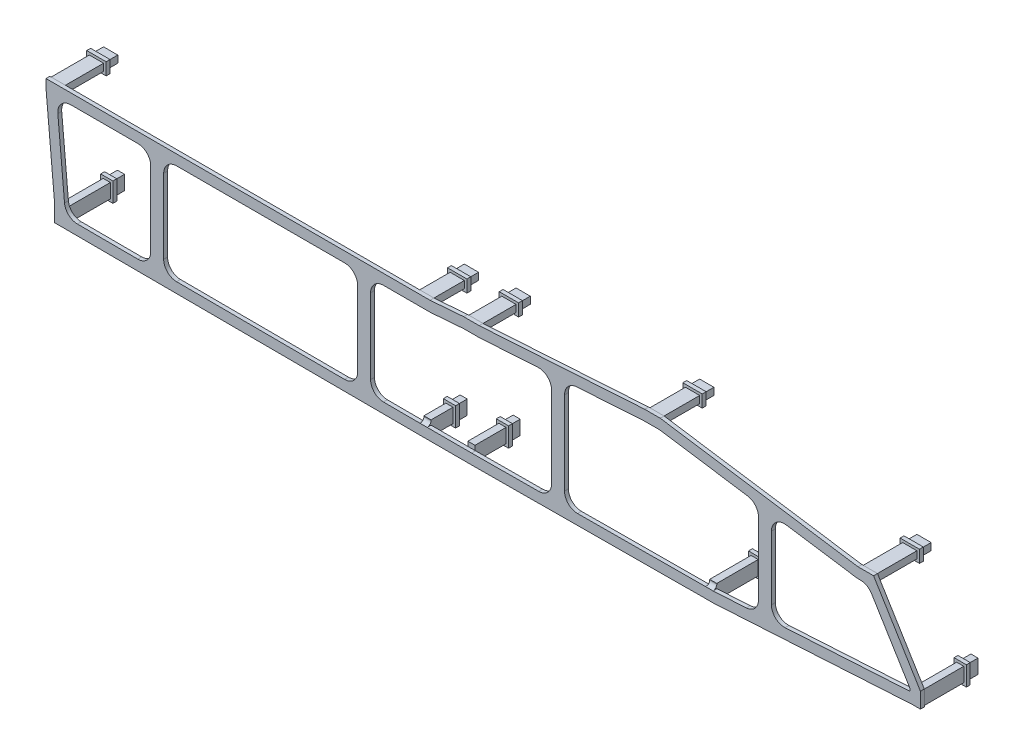
SolidWorks part; units mm, degrees
ref_plane "Front Plane" through (0, 0, 0) normal (0, 0, 1) x (1, 0, 0)
ref_plane "Top Plane" through (0, 0, 0) normal (0, 1, 0) x (1, 0, 0)
ref_plane "Right Plane" through (0, 0, 0) normal (1, 0, 0) x (0, 0, -1)
ref_plane "Plane11" through (0, 0, 7) normal (0, 0, 1) x (1, 0, 0)
ref_plane "Plane12" through (0, 0, 27) normal (0, 0, 1) x (1, 0, 0)
sketch "Sketch13" plane through (0, 0, 27) normal (0, 0, 1) x (1, 0, 0)
  line L0 (-277.75, -90) -> (-284.25, -90)
  line L1 (-284.25, -90) -> (-284.25, -78)
  line L2 (-284.25, -78) -> (-291, -3.25)
  line L3 (-291, -3.25) -> (-291, 3.25)
  line L4 (-291, 3.25) -> (-279, 3.25)
  line L5 (-279, 3.25) -> (-6, 3.25)
  line L6 (-6, 3.25) -> (6, 3.25)
  line L7 (6, 3.25) -> (32, 5.25)
  line L8 (32, 5.25) -> (44, 5.25)
  line L9 (44, 5.25) -> (172, 13.25)
  line L10 (172, 13.25) -> (184, 13.25)
  line L11 (184, 13.25) -> (337, -9.75)
  line L12 (337, -9.75) -> (349, -9.75)
  line L13 (349, -9.75) -> (385.25, -69)
  line L14 (385.25, -69) -> (385.25, -81)
  line L15 (385.25, -81) -> (378.75, -81)
  line L16 (378.75, -81) -> (225.25, -90)
  line L17 (225.25, -90) -> (218.75, -90)
  line L18 (218.75, -90) -> (38.25, -91)
  line L19 (38.25, -91) -> (31.75, -91)
  line L20 (31.75, -91) -> (4.25, -91)
  line L21 (4.25, -91) -> (-2.25, -91)
  line L22 (-2.25, -91) -> (-277.75, -90)
  line L23 (184, 13.25) -> (184, 6.75) construction
extrude "STUD LINK" add sketch "Sketch13" along normal blind 3
ref_plane "Plane1" through (0, 0, 0) normal (0, 0, 1) x (1, 0, 0)
ref_plane "Plane2" through (0, 0, -2) normal (0, 0, 1) x (1, 0, 0)
ref_plane "Plane3" through (0, 0, -4) normal (0, 0, 1) x (1, 0, 0)
ref_plane "Plane4" through (0, 0, 7) normal (0, 0, 1) x (1, 0, 0)
ref_plane "Plane5" through (0, 0, 0) normal (0, 0, 1) x (1, 0, 0)
ref_plane "Plane6" through (0, 0, -8) normal (0, 0, 1) x (1, 0, 0)
ref_plane "Plane7" through (0, 0, -7) normal (0, 0, 1) x (1, 0, 0)
ref_plane "Plane8" through (0, 0, -7) normal (0, 0, 1) x (1, 0, 0)
ref_plane "Plane9" through (0, 0, -6) normal (0, 0, 1) x (1, 0, 0)
ref_plane "Plane10" through (0, 0, -10) normal (0, 0, 1) x (1, 0, 0)
sketch "Sketch1" plane through (0, 0, 0) normal (0, 0, 1) x (1, 0, 0)
  line L8 (-5.5, 2.75) -> (-5.5, -2.75)
  line L9 (-5.5, -2.75) -> (5.5, -2.75)
  line L10 (5.5, -2.75) -> (5.5, 2.75)
  line L11 (5.5, 2.75) -> (-5.5, 2.75)
  line L12 (-5.5, 2.75) -> (-5.5, -2.75)
  line L13 (-5.5, -2.75) -> (5.5, -2.75)
  line L14 (5.5, -2.75) -> (5.5, 2.75)
  line L15 (5.5, 2.75) -> (-5.5, 2.75)
  dimension "D1" = 0.5
extrude "Boss-Extrude1" add sketch "Sketch1" against normal blind 8 and the other way up to next
sketch "Sketch2" plane through (0, 0, -2) normal (0, 0, 1) x (1, 0, 0)
  line L8 (43.5, 4.75) -> (32.5, 4.75)
  line L9 (43.5, -0.75) -> (43.5, 4.75)
  line L10 (32.5, -0.75) -> (43.5, -0.75)
  line L11 (32.5, 4.75) -> (32.5, -0.75)
  line L12 (43.5, 4.75) -> (32.5, 4.75)
  line L13 (43.5, -0.75) -> (43.5, 4.75)
  line L14 (32.5, -0.75) -> (43.5, -0.75)
  line L15 (32.5, 4.75) -> (32.5, -0.75)
  dimension "D1" = 0.5
extrude "Boss-Extrude2" add sketch "Sketch2" against normal blind 8 and the other way up to next separate body
sketch "Sketch3" plane through (0, 0, -4) normal (0, 0, 1) x (1, 0, 0)
  line L16 (183.5, 12.75) -> (172.5, 12.75)
  line L17 (183.5, 7.25) -> (183.5, 12.75)
  line L18 (172.5, 7.25) -> (183.5, 7.25)
  line L19 (172.5, 12.75) -> (172.5, 7.25)
  line L20 (183.5, 12.75) -> (172.5, 12.75)
  line L21 (183.5, 7.25) -> (183.5, 12.75)
  line L22 (172.5, 7.25) -> (183.5, 7.25)
  line L23 (172.5, 12.75) -> (172.5, 7.25)
  dimension "D1" = 0.5
extrude "Boss-Extrude3" add sketch "Sketch3" against normal blind 8 and the other way up to next separate body
sketch "Sketch4" plane through (0, 0, 7) normal (0, 0, 1) x (1, 0, 0)
  line L8 (3.75, -79.5) -> (-1.75, -79.5)
  line L9 (3.75, -90.5) -> (3.75, -79.5)
  line L10 (-1.75, -90.5) -> (3.75, -90.5)
  line L11 (-1.75, -79.5) -> (-1.75, -90.5)
  line L12 (3.75, -79.5) -> (-1.75, -79.5)
  line L13 (3.75, -90.5) -> (3.75, -79.5)
  line L14 (-1.75, -90.5) -> (3.75, -90.5)
  line L15 (-1.75, -79.5) -> (-1.75, -90.5)
  dimension "D1" = 0.5
extrude "Boss-Extrude4" add sketch "Sketch4" against normal blind 8 and the other way up to next separate body
sketch "Sketch5" plane through (0, 0, 0) normal (0, 0, 1) x (1, 0, 0)
  line L16 (32.25, -79.5) -> (32.25, -90.5)
  line L17 (37.75, -79.5) -> (32.25, -79.5)
  line L18 (37.75, -90.5) -> (37.75, -79.5)
  line L19 (32.25, -90.5) -> (37.75, -90.5)
  line L20 (32.25, -79.5) -> (32.25, -90.5)
  line L21 (37.75, -79.5) -> (32.25, -79.5)
  line L22 (37.75, -90.5) -> (37.75, -79.5)
  line L23 (32.25, -90.5) -> (37.75, -90.5)
  dimension "D1" = 0.5
extrude "Boss-Extrude5" add sketch "Sketch5" against normal blind 8 and the other way up to next separate body
sketch "Sketch6" plane through (0, 0, -8) normal (0, 0, 1) x (1, 0, 0)
  line L8 (224.75, -78.5) -> (219.25, -78.5)
  line L9 (219.25, -78.5) -> (219.25, -89.5)
  line L10 (219.25, -89.5) -> (224.75, -89.5)
  line L11 (224.75, -89.5) -> (224.75, -78.5)
  line L12 (224.75, -78.5) -> (219.25, -78.5)
  line L13 (219.25, -78.5) -> (219.25, -89.5)
  line L14 (219.25, -89.5) -> (224.75, -89.5)
  line L15 (224.75, -89.5) -> (224.75, -78.5)
  dimension "D1" = 0.5
extrude "Boss-Extrude6" add sketch "Sketch6" against normal blind 8 and the other way up to next separate body
sketch "Sketch7" plane through (0, 0, -7) normal (0, 0, 1) x (1, 0, 0)
  line L8 (348.5, -10.25) -> (337.5, -10.25)
  line L9 (348.5, -15.75) -> (348.5, -10.25)
  line L10 (337.5, -15.75) -> (348.5, -15.75)
  line L11 (337.5, -10.25) -> (337.5, -15.75)
  line L12 (348.5, -10.25) -> (337.5, -10.25)
  line L13 (348.5, -15.75) -> (348.5, -10.25)
  line L14 (337.5, -15.75) -> (348.5, -15.75)
  line L15 (337.5, -10.25) -> (337.5, -15.75)
  dimension "D1" = 0.5
extrude "Boss-Extrude7" add sketch "Sketch7" against normal blind 8 and the other way up to next separate body
sketch "Sketch8" plane through (0, 0, -7) normal (0, 0, 1) x (1, 0, 0)
  line L8 (384.75, -69.5) -> (379.25, -69.5)
  line L9 (384.75, -80.5) -> (384.75, -69.5)
  line L10 (379.25, -80.5) -> (384.75, -80.5)
  line L11 (379.25, -69.5) -> (379.25, -80.5)
  line L12 (384.75, -69.5) -> (379.25, -69.5)
  line L13 (384.75, -80.5) -> (384.75, -69.5)
  line L14 (379.25, -80.5) -> (384.75, -80.5)
  line L15 (379.25, -69.5) -> (379.25, -80.5)
  dimension "D1" = 0.5
extrude "Boss-Extrude8" add sketch "Sketch8" against normal blind 8 and the other way up to next separate body
sketch "Sketch9" plane through (0, 0, -6) normal (0, 0, 1) x (1, 0, 0)
  line L8 (-279.5, 2.75) -> (-290.5, 2.75)
  line L9 (-279.5, -2.75) -> (-279.5, 2.75)
  line L10 (-290.5, -2.75) -> (-279.5, -2.75)
  line L11 (-290.5, 2.75) -> (-290.5, -2.75)
  line L12 (-279.5, 2.75) -> (-290.5, 2.75)
  line L13 (-279.5, -2.75) -> (-279.5, 2.75)
  line L14 (-290.5, -2.75) -> (-279.5, -2.75)
  line L15 (-290.5, 2.75) -> (-290.5, -2.75)
  dimension "D1" = 0.5
extrude "Boss-Extrude9" add sketch "Sketch9" against normal blind 8 and the other way up to next separate body
sketch "Sketch10" plane through (0, 0, -10) normal (0, 0, 1) x (1, 0, 0)
  line L8 (-278.25, -78.5) -> (-283.75, -78.5)
  line L9 (-278.25, -89.5) -> (-278.25, -78.5)
  line L10 (-283.75, -89.5) -> (-278.25, -89.5)
  line L11 (-283.75, -78.5) -> (-283.75, -89.5)
  line L12 (-278.25, -78.5) -> (-283.75, -78.5)
  line L13 (-278.25, -89.5) -> (-278.25, -78.5)
  line L14 (-283.75, -89.5) -> (-278.25, -89.5)
  line L15 (-283.75, -78.5) -> (-283.75, -89.5)
  dimension "D1" = 0.5
extrude "Boss-Extrude10" add sketch "Sketch10" against normal blind 8 and the other way up to next (37 mm away) separate body
sketch "Sketch14" plane through (0, 0, 0) normal (0, 0, 1) x (1, 0, 0)
  line L8 (-7.5, -4.75) -> (7.5, -4.75)
  line L9 (7.5, -4.75) -> (7.5, 4.75)
  line L10 (7.5, 4.75) -> (-7.5, 4.75)
  line L11 (-7.5, 4.75) -> (-7.5, -4.75)
  line L12 (-7.5, -4.75) -> (7.5, -4.75)
  line L13 (7.5, -4.75) -> (7.5, 4.75)
  line L14 (7.5, 4.75) -> (-7.5, 4.75)
  line L15 (-7.5, 4.75) -> (-7.5, -4.75)
  dimension "D1" = 1.5
extrude "Boss-Extrude14" add sketch "Sketch14" along normal blind 3
sketch "Sketch15" plane through (0, 0, -2) normal (0, 0, 1) x (1, 0, 0)
  line L8 (45.5, 6.75) -> (30.5, 6.75)
  line L9 (30.5, 6.75) -> (30.5, -2.75)
  line L10 (30.5, -2.75) -> (45.5, -2.75)
  line L11 (45.5, -2.75) -> (45.5, 6.75)
  line L12 (45.5, 6.75) -> (30.5, 6.75)
  line L13 (30.5, 6.75) -> (30.5, -2.75)
  line L14 (30.5, -2.75) -> (45.5, -2.75)
  line L15 (45.5, -2.75) -> (45.5, 6.75)
  dimension "D1" = 1.5
extrude "Boss-Extrude15" add sketch "Sketch15" along normal blind 3
sketch "Sketch16" plane through (0, 0, -4) normal (0, 0, 1) x (1, 0, 0)
  line L16 (185.5, 14.75) -> (170.5, 14.75)
  line L17 (185.5, 5.25) -> (185.5, 14.75)
  line L18 (170.5, 5.25) -> (185.5, 5.25)
  line L19 (170.5, 14.75) -> (170.5, 5.25)
  line L20 (185.5, 14.75) -> (170.5, 14.75)
  line L21 (185.5, 5.25) -> (185.5, 14.75)
  line L22 (170.5, 5.25) -> (185.5, 5.25)
  line L23 (170.5, 14.75) -> (170.5, 5.25)
  dimension "D1" = 1.5
extrude "Boss-Extrude16" add sketch "Sketch16" along normal blind 3
sketch "Sketch17" plane through (0, 0, 7) normal (0, 0, 1) x (1, 0, 0)
  line L8 (5.75, -77.5) -> (-3.75, -77.5)
  line L9 (-3.75, -77.5) -> (-3.75, -92.5)
  line L10 (-3.75, -92.5) -> (5.75, -92.5)
  line L11 (5.75, -92.5) -> (5.75, -77.5)
  line L12 (5.75, -77.5) -> (-3.75, -77.5)
  line L13 (-3.75, -77.5) -> (-3.75, -92.5)
  line L14 (-3.75, -92.5) -> (5.75, -92.5)
  line L15 (5.75, -92.5) -> (5.75, -77.5)
  dimension "D1" = 1.5
extrude "Boss-Extrude17" add sketch "Sketch17" along normal blind 3
sketch "Sketch18" plane through (0, 0, 0) normal (0, 0, 1) x (1, 0, 0)
  line L8 (39.75, -77.5) -> (30.25, -77.5)
  line L9 (39.75, -92.5) -> (39.75, -77.5)
  line L10 (30.25, -92.5) -> (39.75, -92.5)
  line L11 (30.25, -77.5) -> (30.25, -92.5)
  line L16 (39.75, -77.5) -> (30.25, -77.5)
  line L17 (39.75, -92.5) -> (39.75, -77.5)
  line L18 (30.25, -92.5) -> (39.75, -92.5)
  line L19 (30.25, -77.5) -> (30.25, -92.5)
  dimension "D1" = 1.5
extrude "Boss-Extrude18" add sketch "Sketch18" along normal blind 3
sketch "Sketch19" plane through (0, 0, -8) normal (0, 0, 1) x (1, 0, 0)
  line L8 (226.75, -76.5) -> (217.25, -76.5)
  line L9 (226.75, -91.5) -> (226.75, -76.5)
  line L10 (217.25, -91.5) -> (226.75, -91.5)
  line L11 (217.25, -76.5) -> (217.25, -91.5)
  line L12 (226.75, -76.5) -> (217.25, -76.5)
  line L13 (226.75, -91.5) -> (226.75, -76.5)
  line L14 (217.25, -91.5) -> (226.75, -91.5)
  line L15 (217.25, -76.5) -> (217.25, -91.5)
  dimension "D1" = 1.5
extrude "Boss-Extrude19" add sketch "Sketch19" along normal blind 3
sketch "Sketch20" plane through (0, 0, -7) normal (0, 0, 1) x (1, 0, 0)
  line L8 (350.5, -8.25) -> (335.5, -8.25)
  line L9 (335.5, -8.25) -> (335.5, -17.75)
  line L10 (335.5, -17.75) -> (350.5, -17.75)
  line L11 (350.5, -17.75) -> (350.5, -8.25)
  line L12 (350.5, -8.25) -> (335.5, -8.25)
  line L13 (335.5, -8.25) -> (335.5, -17.75)
  line L14 (335.5, -17.75) -> (350.5, -17.75)
  line L15 (350.5, -17.75) -> (350.5, -8.25)
  dimension "D1" = 1.5
extrude "Boss-Extrude20" add sketch "Sketch20" along normal blind 3
sketch "Sketch21" plane through (0, 0, -7) normal (0, 0, 1) x (1, 0, 0)
  line L8 (386.75, -67.5) -> (377.25, -67.5)
  line L9 (386.75, -82.5) -> (386.75, -67.5)
  line L10 (377.25, -82.5) -> (386.75, -82.5)
  line L11 (377.25, -67.5) -> (377.25, -82.5)
  line L12 (386.75, -67.5) -> (377.25, -67.5)
  line L13 (386.75, -82.5) -> (386.75, -67.5)
  line L14 (377.25, -82.5) -> (386.75, -82.5)
  line L15 (377.25, -67.5) -> (377.25, -82.5)
  dimension "D1" = 1.5
extrude "Boss-Extrude21" add sketch "Sketch21" along normal blind 3
sketch "Sketch22" plane through (0, 0, -6) normal (0, 0, 1) x (1, 0, 0)
  line L8 (-277.5, 4.75) -> (-292.5, 4.75)
  line L9 (-277.5, -4.75) -> (-277.5, 4.75)
  line L10 (-292.5, -4.75) -> (-277.5, -4.75)
  line L11 (-292.5, 4.75) -> (-292.5, -4.75)
  line L12 (-277.5, 4.75) -> (-292.5, 4.75)
  line L13 (-277.5, -4.75) -> (-277.5, 4.75)
  line L14 (-292.5, -4.75) -> (-277.5, -4.75)
  line L15 (-292.5, 4.75) -> (-292.5, -4.75)
  dimension "D1" = 1.5
extrude "Boss-Extrude22" add sketch "Sketch22" along normal blind 3
sketch "Sketch23" plane through (0, 0, -10) normal (0, 0, 1) x (1, 0, 0)
  line L15 (-276.25, -76.5) -> (-285.75, -76.5)
  line L16 (-285.75, -76.5) -> (-285.75, -91.5)
  line L17 (-276.25, -91.5) -> (-276.25, -76.5)
  line L18 (-285.75, -91.5) -> (-276.25, -91.5)
  line L19 (-276.25, -76.5) -> (-285.75, -76.5)
  line L20 (-285.75, -76.5) -> (-285.75, -91.5)
  line L21 (-276.25, -91.5) -> (-276.25, -76.5)
  line L22 (-285.75, -91.5) -> (-276.25, -91.5)
  dimension "D1" = 1.5
extrude "Boss-Extrude23" add sketch "Sketch23" along normal blind 3
sketch "Sketch24" plane through (0, 0, 30) normal (0, 0, 1) x (1, 0, 0)
  line L42 (-276.25, -82.0054) -> (-2.2355, -83)
  line L43 (-2.2355, -83) -> (38.2278, -83)
  line L46 (38.2278, -83) -> (218.7278, -82)
  line L47 (218.7278, -82) -> (225.0157, -82)
  line L48 (225.0157, -82) -> (377.25, -73.0742)
  line L49 (377.25, -73.0742) -> (377.25, -71.2531)
  line L50 (377.25, -71.2531) -> (344.516, -17.75)
  line L51 (344.516, -17.75) -> (336.4021, -17.75)
  line L52 (336.4021, -17.75) -> (183.4021, 5.25)
  line L53 (183.4021, 5.25) -> (172.2498, 5.25)
  line L54 (172.2498, 5.25) -> (44.2498, -2.75)
  line L55 (44.2498, -2.75) -> (32.3072, -2.75)
  line L56 (32.3072, -2.75) -> (6.3072, -4.75)
  line L57 (6.3072, -4.75) -> (-282.832, -4.75)
  line L58 (-282.832, -4.75) -> (-276.25, -77.6395)
  line L59 (-276.25, -77.6395) -> (-276.25, -82.0054)
  line L60 (-276.25, -82.0054) -> (-2.2355, -83)
  line L61 (-2.2355, -83) -> (38.2278, -83)
  line L64 (38.2278, -83) -> (218.7278, -82)
  line L65 (218.7278, -82) -> (225.0157, -82)
  line L66 (225.0157, -82) -> (377.25, -73.0742)
  line L67 (377.25, -73.0742) -> (377.25, -71.2531)
  line L68 (377.25, -71.2531) -> (344.516, -17.75)
  line L69 (344.516, -17.75) -> (336.4021, -17.75)
  line L70 (336.4021, -17.75) -> (183.4021, 5.25)
  line L71 (183.4021, 5.25) -> (172.2498, 5.25)
  line L72 (172.2498, 5.25) -> (44.2498, -2.75)
  line L73 (44.2498, -2.75) -> (32.3072, -2.75)
  line L74 (32.3072, -2.75) -> (6.3072, -4.75)
  line L75 (6.3072, -4.75) -> (-282.832, -4.75)
  line L76 (-282.832, -4.75) -> (-276.25, -77.6395)
  line L77 (-276.25, -77.6395) -> (-276.25, -82.0054)
  dimension "D1" = 8
extrude "Cut-Extrude1" cut sketch "Sketch24" against normal blind 3
ref_plane "Plane13" through (0, -50, 0) normal (0, 1, 0) x (1, 0, 0)
sketch "Sketch25" plane through (0, -50, 0) normal (0, 1, 0) x (1, 0, 0)
  line L0 (6, -27) -> (-291, -27) construction
  line L1 (-210, -27) -> (-200, -27)
  line L2 (-210, -27) -> (-210, -30)
  line L3 (-210, -30) -> (-200, -30)
  line L4 (-200, -27) -> (-200, -30)
  line L5 (6, -30) -> (-291, -30) construction
  line L6 (172, -27) -> (44, -27) construction
  line L7 (-50, -27) -> (-40, -27)
  line L8 (-50, -27) -> (-50, -30)
  line L9 (-50, -30) -> (-40, -30)
  line L10 (-40, -27) -> (-40, -30)
  line L11 (100, -27) -> (110, -27)
  line L12 (100, -27) -> (100, -30)
  line L13 (100, -30) -> (110, -30)
  line L14 (110, -27) -> (110, -30)
  line L15 (172, -30) -> (44, -30) construction
  line L16 (337, -27) -> (184, -27) construction
  line L17 (260, -27) -> (270, -27)
  line L18 (260, -27) -> (260, -30)
  line L19 (260, -30) -> (270, -30)
  line L20 (270, -27) -> (270, -30)
  line L21 (337, -30) -> (184, -30) construction
  dimension "D1" = 10
  dimension "D2" = 150
  dimension "D3" = 40
  dimension "D4" = 100
  dimension "D5" = 150
extrude "Boss-Extrude24" add sketch "Sketch25" along normal up to next and the other way up to next
fillet "Fillet1" radius 3 2 edges at (222, -82, 27) (1, -83, 27)
fillet "Fillet2" radius 10 20 edges at (-210, -82.2459, 28.5) (-210, -4.75, 28.5) (-282.832, -4.75, 28.5) (-276.25, -82.0054, 28.5) (100, -82.6578, 28.5) (100, 0.7344, 28.5) (-50, -4.75, 28.5) (-50, -82.8266, 28.5) (-40, -82.8629, 28.5) (-200, -82.2822, 28.5) (-200, -4.75, 28.5) (-40, -4.75, 28.5) (110, 1.3594, 28.5) (110, -82.6024, 28.5) (270, -79.3625, 28.5) (260, -79.9488, 28.5) (260, -6.2647, 28.5) (270, -7.768, 28.5) (336.4021, -17.75, 28.5) (344.516, -17.75, 28.5)
ref_plane "Plane14" through (18, 0, 0) normal (-1, 0, 0) x (0, 0, 1)
sketch "Sketch26" plane through (18, 0, 0) normal (-1, 0, 0) x (0, 0, 1)
  line L1 (-177.7155, 99.6631) -> (210.2216, 99.6631)
  line L2 (-177.7155, 99.6631) -> (-177.7155, -244.2201)
  line L3 (-177.7155, -244.2201) -> (210.2216, -244.2201)
  line L4 (210.2216, 99.6631) -> (210.2216, -244.2201)
extrude "Cut-Extrude2" [suppressed] cut sketch "Sketch26" against normal through all
